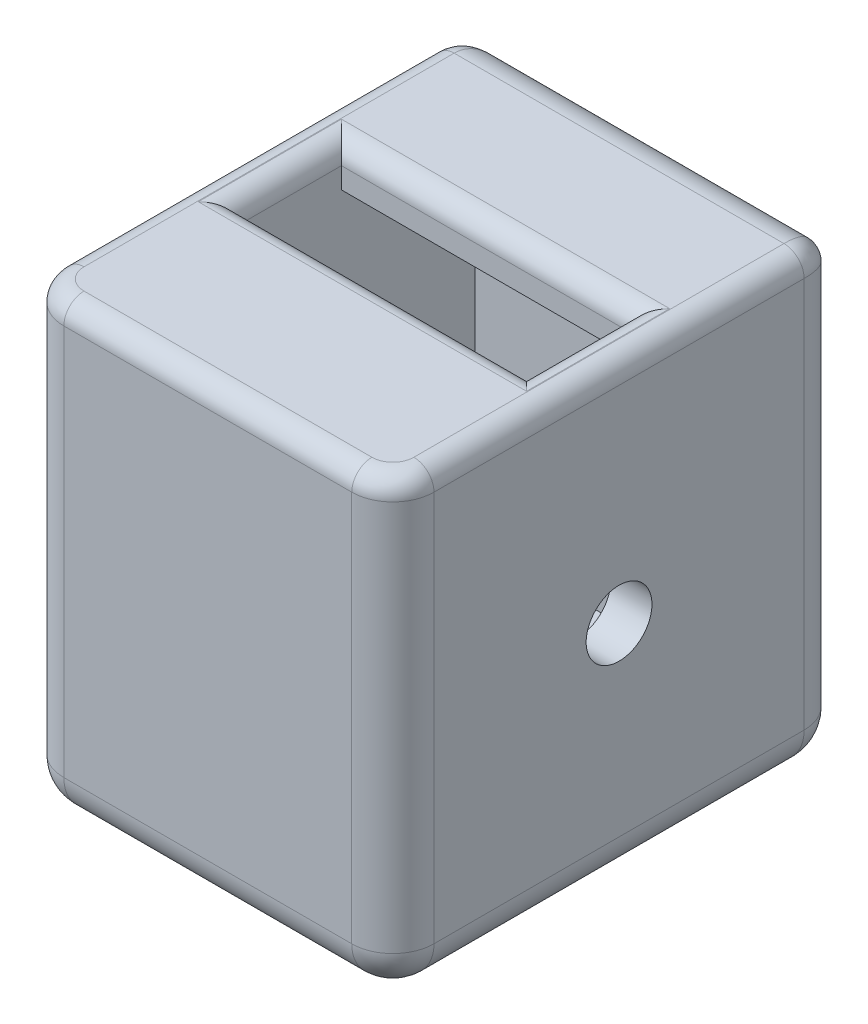
SolidWorks part; units mm, degrees
material "POLYURETHANE (11671)"
ref_plane "Front Plane" through (0, 0, 0) normal (0, 0, 1) x (1, 0, 0)
ref_plane "Top Plane" through (0, 0, 0) normal (0, 1, 0) x (1, 0, 0)
ref_plane "Right Plane" through (0, 0, 0) normal (1, 0, 0) x (0, 0, -1)
sketch "Sketch2" plane through (0, 0, 0) normal (0, 1, 0) x (1, 0, 0)
  line L0 (-8.89, 11.43) -> (-8.89, 13.97) construction
  line L1 (8.89, 11.43) -> (-8.89, 11.43)
  line L2 (8.89, 11.43) -> (8.89, -11.43)
  line L3 (8.89, -11.43) -> (-8.89, -11.43)
  line L4 (-8.89, 11.43) -> (-8.89, -11.43)
  line L5 (11.43, 13.97) -> (-11.43, 13.97)
  line L6 (11.43, 13.97) -> (11.43, -13.97)
  line L7 (11.43, -13.97) -> (-11.43, -13.97)
  line L8 (-11.43, 13.97) -> (-11.43, -13.97)
  line L9 (-8.89, 11.43) -> (-11.43, 11.43) construction
  point P8 (0, 13.97)
  point P9 (0, 11.43)
  point P11 (-8.89, 0)
  point P12 (-11.43, 0)
  dimension "D1" = 17.78
  dimension "D2" = 22.86
  dimension "D3" = 2.54
extrude "Boss-Extrude1" add sketch "Sketch2" along normal mid plane 27.94
sketch "Sketch3" plane through (0, -13.97, 0) normal (0, -1, 0) x (1, 0, 0)
  line L1 (-8.89, 11.43) -> (8.89, 11.43)
  line L2 (-8.89, 11.43) -> (-8.89, -11.43)
  line L3 (-8.89, -11.43) -> (8.89, -11.43)
  line L4 (8.89, 11.43) -> (8.89, -11.43)
extrude "Boss-Extrude2" add sketch "Sketch3" against normal blind 2.54
sketch "Sketch4" plane through (0, 13.97, 0) normal (0, 1, 0) x (1, 0, 0)
  line L0 (8.89, -11.43) -> (8.89, 11.43) construction
  line L1 (-8.89, 11.43) -> (8.89, 11.43)
  line L2 (-8.89, 11.43) -> (-8.89, 3.175)
  line L3 (-8.89, 3.175) -> (8.89, 3.175)
  line L4 (8.89, 11.43) -> (8.89, 3.175)
  line L11 (-8.89, -11.43) -> (8.89, -11.43) construction
  line L12 (-8.89, -11.43) -> (8.89, -11.43)
  line L13 (-8.89, -11.43) -> (-8.89, -3.175)
  line L14 (-8.89, -3.175) -> (8.89, -3.175)
  line L15 (8.89, -11.43) -> (8.89, -3.175)
  line L16 (8.89, -11.43) -> (-8.89, -11.43) construction
  dimension "D1" = 6.35
extrude "Boss-Extrude3" add sketch "Sketch4" against normal blind 2.54
sketch "Sketch5" plane through (-11.43, 0, 0) normal (-1, 0, 0) x (0, 0, 1)
  line L1 (-13.97, -13.97) -> (13.97, -13.97)
  line L2 (-13.97, -13.97) -> (-13.97, 13.97)
  line L3 (-13.97, 13.97) -> (13.97, 13.97)
  line L4 (13.97, -13.97) -> (13.97, 13.97)
  line L5 (-13.97, -13.97) -> (13.97, 13.97) construction
  line L6 (-13.97, 13.97) -> (13.97, -13.97) construction
  circle A0 centre (0, 0) radius 10.033
  point P0 (0, 0)
  dimension "D1" = 20.066
extrude "Cut-Extrude1" [suppressed] cut sketch "Sketch5" against normal up to surface (2.54 mm away) contours A0
sketch "Sketch6" plane through (11.43, 0, 0) normal (1, 0, 0) x (0, 0, -1)
  line L1 (-13.97, -13.97) -> (13.97, -13.97)
  line L2 (-13.97, -13.97) -> (-13.97, 13.97)
  line L3 (-13.97, 13.97) -> (13.97, 13.97)
  line L4 (13.97, -13.97) -> (13.97, 13.97)
  line L5 (-13.97, -13.97) -> (13.97, 13.97) construction
  line L6 (-13.97, 13.97) -> (13.97, -13.97) construction
  circle A0 centre (0, 0) radius 2.032
  point P0 (0, 0)
  dimension "D1" = 4.064
extrude "Cut-Extrude2" cut sketch "Sketch6" against normal up to surface (2.54 mm away) contours A0 region at (11.43, 0, 0) up to face at (8.89, 6.35, 0)
sketch "Sketch7" plane through (0, 0, -13.97) normal (0, 0, -1) x (-1, 0, 0)
  line L0 (-11.43, 13.97) -> (-11.43, -13.97) construction
  line L1 (-5.715, -3.175) -> (-2.54, -3.175)
  line L2 (-5.715, -3.175) -> (-5.715, 3.175)
  line L3 (-5.715, 3.175) -> (-2.54, 3.175)
  line L4 (-2.54, -3.175) -> (-2.54, 3.175)
  line L5 (-5.715, -3.175) -> (-2.54, 3.175) construction
  line L6 (-5.715, 3.175) -> (-2.54, -3.175) construction
  point P0 (-4.1275, 0)
  dimension "D1" = 3.175
  dimension "D2" = 5.715
  dimension "D3" = 6.35
extrude "Cut-Extrude3" cut sketch "Sketch7" against normal up to surface (2.54 mm away) contours L4 L3 L2 L1 up to face at (0, 0, -11.43)
sketch "Sketch10" [suppressed] plane through (0, 0, 13.97) normal (0, 0, 1) x (1, 0, 0)
  line L0 (10.16, 13.97) -> (10.16, -13.97) construction
  line L1 (1.27, -3.175) -> (4.445, -3.175)
  line L2 (1.27, -3.175) -> (1.27, 3.175)
  line L3 (1.27, 3.175) -> (4.445, 3.175)
  line L4 (4.445, -3.175) -> (4.445, 3.175)
  line L5 (1.27, -3.175) -> (4.445, 3.175) construction
  line L6 (1.27, 3.175) -> (4.445, -3.175) construction
  point P0 (2.8575, 0)
  dimension "D1" = 5.715
  dimension "D2" = 3.175
  dimension "D3" = 6.35
extrude "Cut-Extrude4" [suppressed] cut sketch "Sketch10" against normal up to next
fillet "Fillet1" radius 2.54 9 edges at (-11.43, 0, -13.97) (-11.43, 0, 13.97) (11.43, 0, -13.97) (11.43, 0, 13.97) (0, 13.97, -13.97) (-11.43, -13.97, 0) (11.43, -13.97, 0) (0, -13.97, 13.97) (0, -13.97, -13.97)
fillet "Fillet2" radius 1.2446 11 edges at (-10.6861, 13.2261, -13.2261) (-11.43, 13.97, 0) (-10.6861, 13.97, 13.2261) (0, 13.97, 13.97) (10.6861, 13.97, 13.2261) (10.6861, 13.2261, -13.2261) (-8.89, 13.97, 0) (8.89, 13.97, 0) (0, 13.97, -3.175) (11.43, 13.97, 0) (0, 13.97, 3.175)
